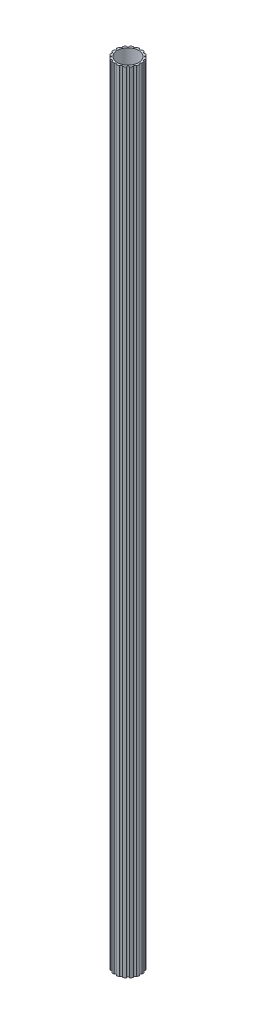
SolidWorks part; units mm, degrees
material "Plain Carbon Steel"
ref_plane "Front Plane" through (0, 0, 0) normal (0, 0, 1) x (1, 0, 0)
ref_plane "Top Plane" through (0, 0, 0) normal (0, 1, 0) x (1, 0, 0)
ref_plane "Right Plane" through (0, 0, 0) normal (1, 0, 0) x (0, 0, -1)
sketch "Sketch1" plane through (0, 0, 0) normal (0, 1, 0) x (1, 0, 0)
  circle A0 centre (0, 0) radius 17.4625
  circle A1 centre (0, 0) radius 14.4145
  dimension "D1" = 34.925
  dimension "D2" = 28.829
extrude "Boss-Extrude1" add sketch "Sketch1" along normal blind 1070
sketch "Sketch2" plane through (0, 0, 0) normal (0, 1, 0) x (1, 0, 0)
  circle A0 centre (17.4625, 0) radius 1.5
  dimension "D1" = 3
extrude "Cut-Extrude2" cut sketch "Sketch2" against normal blind 1070 and the other way blind 1070
ref_axis "Axis1" through (0, 1123.5, 0) along (0, -1, 0)
pattern_circular "CirPattern1" count 16 over 360 about axis through (0, 1123.5, 0) along (0, -1, 0) of "Cut-Extrude2"
